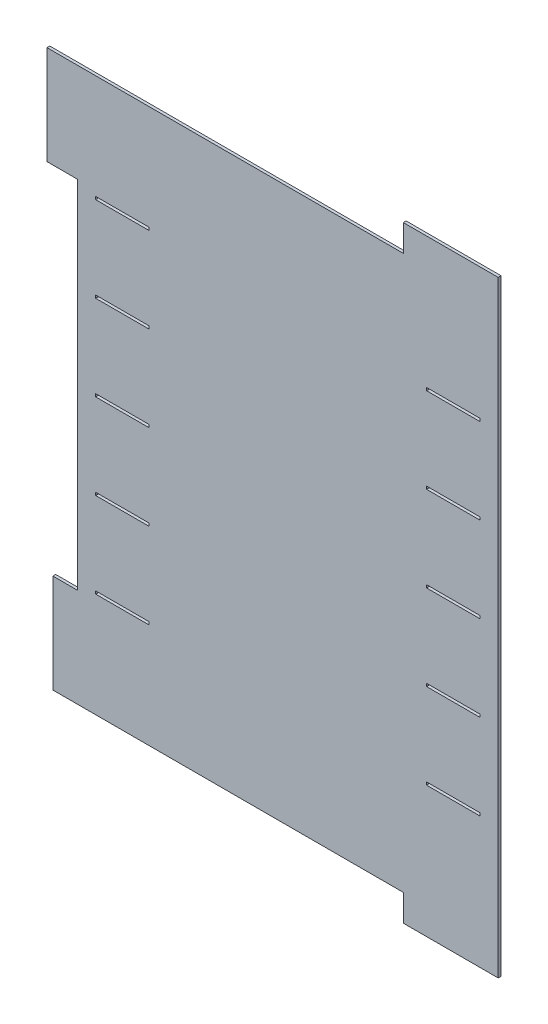
SolidWorks part; units mm, degrees
material "6061-T6 (SS)"
ref_plane "X-Y Datum" through (0, 0, 0) normal (0, 0, 1) x (1, 0, 0)
ref_plane "X-Z Datum" through (0, 0, 0) normal (0, 1, 0) x (1, 0, 0)
ref_plane "Y-Z Datum" through (0, 0, 0) normal (1, 0, 0) x (0, 0, -1)
sketch "Sketch1" plane through (0, 0, 0) normal (0, 0, 1) x (1, 0, 0)
  line L1 (-237.7745, 312.7426) -> (237.7745, 312.7426)
  line L2 (-237.7745, 312.7426) -> (-237.7745, -312.7426)
  line L3 (-237.7745, -312.7426) -> (237.7745, -312.7426)
  line L4 (237.7745, 312.7426) -> (237.7745, -312.7426)
  line L5 (-237.7745, 312.7426) -> (237.7745, -312.7426) construction
  line L6 (-237.7745, -312.7426) -> (237.7745, 312.7426) construction
  point P0 (0, 0)
  dimension "D1" = 475.549
  dimension "D2" = 625.4852
base flange "Base-Flange1" sketch "Sketch1" thickness 3.175 reverse thickness direction no parameters "D1"=1
sketch "Sketch2" plane through (0, 0, 0) normal (0, 0, 1) x (1, 0, 0)
  line L0 (-156.812, 98.1075) -> (-217.137, 98.1075)
  line L1 (237.7745, -312.7426) -> (237.7745, 312.7426) construction
  line L2 (-237.7745, 312.7426) -> (-237.7745, -312.7426) construction
  line L3 (-237.7745, 0) -> (237.7745, 0) construction
  line L4 (-217.137, 1.5875) -> (-217.137, -1.5875)
  line L5 (-217.137, -1.5875) -> (-156.812, -1.5875)
  line L6 (-217.137, 94.9325) -> (-156.812, 94.9325)
  line L11 (0, -43.0151) -> (0, 43.0151) construction
  line L40 (-237.7745, 96.52) -> (237.7745, 96.52) construction
  line L73 (-156.812, 94.9325) -> (-156.812, 98.1075)
  line L74 (-156.812, -1.5875) -> (-156.812, 1.5875)
  line L76 (-156.812, 1.5875) -> (-217.137, 1.5875)
  line L94 (156.812, -1.5875) -> (156.812, 1.5875)
  line L95 (217.137, 1.5875) -> (217.137, -1.5875)
  line L96 (217.137, -1.5875) -> (156.812, -1.5875)
  line L97 (156.812, 1.5875) -> (217.137, 1.5875)
  line L98 (-217.137, 98.1075) -> (-217.137, 94.9325)
  line L99 (156.812, 98.1075) -> (217.137, 98.1075)
  line L100 (217.137, 98.1075) -> (217.137, 94.9325)
  line L101 (217.137, 94.9325) -> (156.812, 94.9325)
  line L102 (156.812, 94.9325) -> (156.812, 98.1075)
  line L103 (-156.812, 194.6275) -> (-217.137, 194.6275)
  line L104 (-217.137, 191.4525) -> (-156.812, 191.4525)
  line L105 (-237.7745, 193.04) -> (237.7745, 193.04) construction
  line L106 (-156.812, 191.4525) -> (-156.812, 194.6275)
  line L107 (-217.137, 194.6275) -> (-217.137, 191.4525)
  line L108 (156.812, 194.6275) -> (217.137, 194.6275)
  line L109 (217.137, 194.6275) -> (217.137, 191.4525)
  line L110 (217.137, 191.4525) -> (156.812, 191.4525)
  line L111 (156.812, 191.4525) -> (156.812, 194.6275)
  line L112 (-237.7745, -96.52) -> (237.7745, -96.52) construction
  line L113 (-156.812, -94.9325) -> (-217.137, -94.9325)
  line L114 (-217.137, -98.1075) -> (-156.812, -98.1075)
  line L115 (-217.137, -94.9325) -> (-217.137, -98.1075)
  line L116 (-156.812, -98.1075) -> (-156.812, -94.9325)
  line L117 (217.137, -98.1075) -> (156.812, -98.1075)
  line L118 (156.812, -94.9325) -> (217.137, -94.9325)
  line L119 (217.137, -94.9325) -> (217.137, -98.1075)
  line L120 (156.812, -98.1075) -> (156.812, -94.9325)
  line L121 (-237.7745, -193.04) -> (237.7745, -193.04) construction
  line L122 (-156.812, -191.4525) -> (-217.137, -191.4525)
  line L123 (-217.137, -194.6275) -> (-156.812, -194.6275)
  line L124 (-217.137, -191.4525) -> (-217.137, -194.6275)
  line L125 (-156.812, -194.6275) -> (-156.812, -191.4525)
  line L126 (217.137, -194.6275) -> (156.812, -194.6275)
  line L127 (156.812, -191.4525) -> (217.137, -191.4525)
  line L128 (217.137, -191.4525) -> (217.137, -194.6275)
  line L129 (156.812, -194.6275) -> (156.812, -191.4525)
  point P11 (-217.137, 0)
  point P30 (-186.9745, -1.5875)
  point P36 (0, 0)
  dimension "D1" = 3
  dimension "D7" = 3.175
  dimension "D8" = 60.325
  dimension "D9" = 50.8
  dimension "D2" = 3
extrude "Cut-Extrude1" cut sketch "Sketch2" against normal through all both and the other way through all normal cut yes
sketch "Sketch3" plane through (0, 0, 0) normal (0, 0, 1) x (1, 0, 0)
  line L1 (237.7745, 312.7426) -> (130.4874, 312.7426)
  line L2 (237.7745, 312.7426) -> (237.7745, 342.9051)
  line L3 (237.7745, 342.9051) -> (130.4874, 342.9051)
  line L4 (130.4874, 312.7426) -> (130.4874, 342.9051)
  line L5 (-237.7745, 312.7426) -> (-272.2474, 312.7426)
  line L6 (-237.7745, 312.7426) -> (-237.7745, 201.1451)
  line L7 (-237.7745, 201.1451) -> (-272.2474, 201.1451)
  line L8 (-272.2474, 312.7426) -> (-272.2474, 201.1451)
  line L9 (-237.7745, -312.7426) -> (-265.6434, -312.7426)
  line L10 (-237.7745, -312.7426) -> (-237.7745, -201.1451)
  line L11 (-237.7745, -201.1451) -> (-265.6434, -201.1451)
  line L12 (-265.6434, -312.7426) -> (-265.6434, -201.1451)
  line L13 (237.7745, -312.7426) -> (130.4874, -312.7426)
  line L14 (237.7745, -312.7426) -> (237.7745, -342.9051)
  line L15 (237.7745, -342.9051) -> (130.4874, -342.9051)
  line L16 (130.4874, -312.7426) -> (130.4874, -342.9051)
extrude "Boss-Extrude1" add sketch "Sketch3" against normal up to surface (3.175 mm away) up to face at (186.9745, 193.04, -3.175)
sketch "Bend-Lines1" [suppressed] plane through (0, 0, 0) normal (0, 1, 0) x (1, 0, 0)
sketch "Bounding-Box1" [suppressed] plane through (0, 0, 0) normal (0, 1, 0) x (1, 0, 0)
sheet metal parameters "Sheet-Metal1" thickness 3.175 parameters "D1"=1
flat pattern "Flat-Pattern1" [suppressed]
sketch "Bend-Lines2" plane through (0, 0, 0) normal (0, 1, 0) x (1, 0, 0)
sketch3d "Bounding-Box2" [suppressed]
  line L0 (232.0925, 287.655, 0) -> (232.0925, -287.655, 0) construction
  line L1 (-232.0925, 287.655, 0) -> (-232.0925, -287.655, 0) construction
  line L2 (232.0925, 287.655, 0) -> (-232.0925, 287.655, 0) construction
  line L3 (232.0925, -287.655, 0) -> (-232.0925, -287.655, 0) construction
sheet metal parameters "Sheet-Metal2" thickness 3.175 parameters "D1"=1
flat pattern "Flat-Pattern1"
sketch "Bend-Lines2" plane through (0, 0, 0) normal (0, 1, 0) x (1, 0, 0)
sketch3d "Bounding-Box2" [suppressed]
  line L0 (236.6874, 307.3451, 0) -> (236.6874, -307.3451, 0) construction
  line L1 (-236.6874, 307.3451, 0) -> (-236.6874, -307.3451, 0) construction
  line L2 (236.6874, 307.3451, 0) -> (-236.6874, 307.3451, 0) construction
  line L3 (236.6874, -307.3451, 0) -> (-236.6874, -307.3451, 0) construction
sheet metal parameters "Sheet-Metal3" thickness 3.175 parameters "D1"=1
flat pattern "Flat-Pattern1"
sketch "Bend-Lines2" plane through (0, 0, 0) normal (0, 1, 0) x (1, 0, 0)
sketch3d "Bounding-Box2" [suppressed]
  line L0 (237.7745, 342.9051, 0) -> (237.7745, -342.9051, 0) construction
  line L1 (-272.2474, 342.9051, 0) -> (-272.2474, -342.9051, 0) construction
  line L2 (237.7745, 342.9051, 0) -> (-272.2474, 342.9051, 0) construction
  line L3 (237.7745, -342.9051, 0) -> (-272.2474, -342.9051, 0) construction
